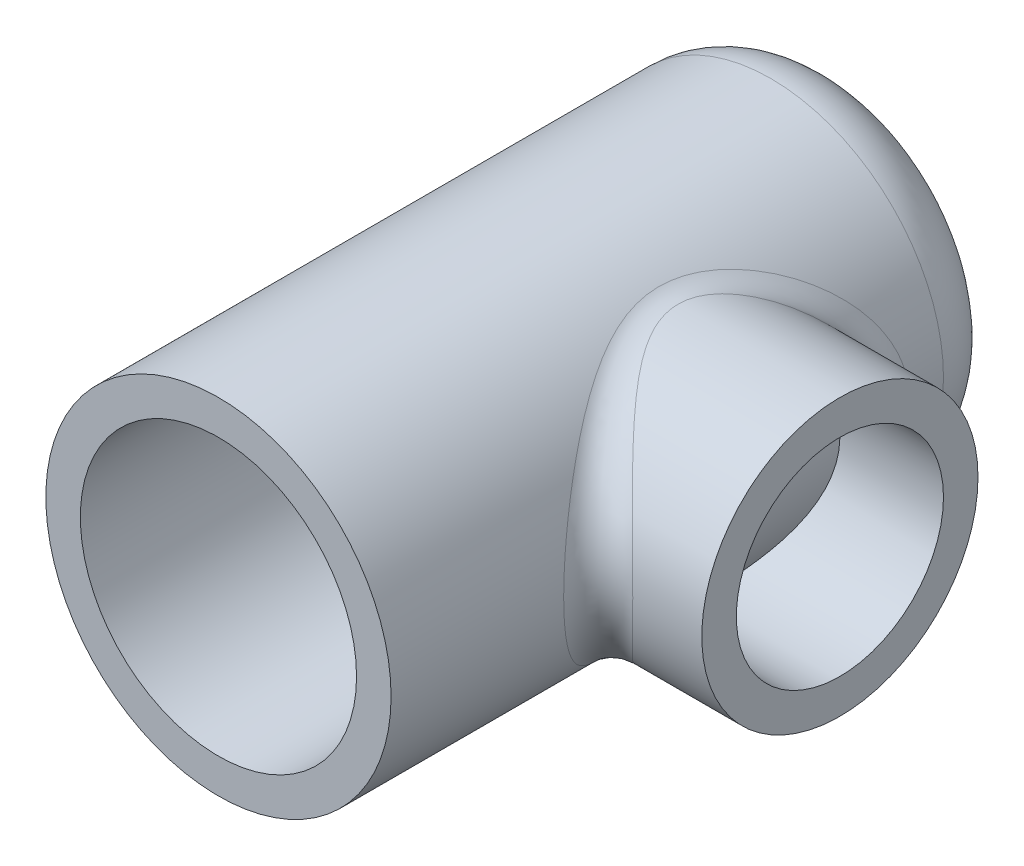
SolidWorks part; units mm, degrees
ref_plane "Front Plane" through (0, 0, 0) normal (0, 0, 1) x (1, 0, 0)
ref_plane "Top Plane" through (0, 0, 0) normal (0, 1, 0) x (1, 0, 0)
ref_plane "Right Plane" through (0, 0, 0) normal (1, 0, 0) x (0, 0, -1)
sketch "Sketch1" plane through (0, 0, 0) normal (0, 1, 0) x (1, 0, 0)
  line L0 (0, 0) -> (0, -80) construction
  line L1 (0, 0) -> (0, -30) construction
  line L2 (0, -30) -> (40, -30) construction
  dimension "D1" = 80
  dimension "D2" = 30
  dimension "D3" = 40
ref_plane "Plane1" through (0, 0, 80) normal (0, 0, 1) x (1, 0, 0)
sketch "Sketch2" plane through (0, 0, 80) normal (0, 0, 1) x (1, 0, 0)
  circle A0 centre (0, 0) radius 25
  circle A1 centre (0, 0) radius 20
extrude "Boss-Extrude1" add sketch "Sketch2" against normal up to vertex (80 mm away) up to point (0, 0, 0)
ref_plane "Plane2" through (40, 0, 30) normal (1, 0, 0) x (0, 0, -1)
sketch "Sketch3" plane through (40, 0, 30) normal (1, 0, 0) x (0, 0, -1)
  circle A0 centre (0, 0) radius 20
  circle A1 centre (0, 0) radius 15
extrude "Boss-Extrude2" add sketch "Sketch3" against normal up to surface (15 mm away) up to face at (25, 0, 0)
sketch "Sketch4" plane through (0, 0, 0) normal (0, 0, -1) x (-1, 0, 0)
  circle A0 centre (0, 0) radius 25
extrude "Boss-Extrude3" add sketch "Sketch4" along normal blind 10
fillet "Fillet1" radius 10 1 edges at (-25, 0, -10)
fillet "Fillet2" radius 5 1 edges at (24.89, -2.3429, 49.8623)
